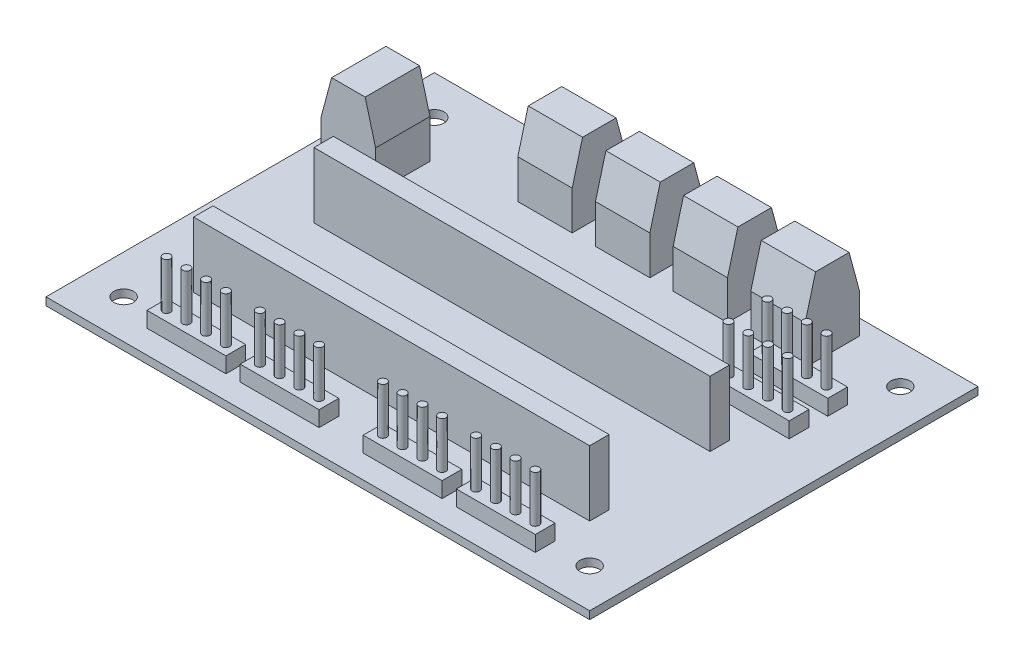
SolidWorks part; units mm, degrees
material "ABS"
ref_plane "Спереди" through (0, 0, 0) normal (0, 0, 1) x (1, 0, 0)
ref_plane "Сверху" through (0, 0, 0) normal (0, 1, 0) x (1, 0, 0)
ref_plane "Справа" through (0, 0, 0) normal (1, 0, 0) x (0, 0, -1)
sketch "Эскиз2" plane through (0, 0, 0) normal (0, 1, 0) x (1, 0, 0)
  line L0 (0, 25) -> (113.3637, 25) construction
  line L1 (0, 0) -> (70, 0)
  line L2 (0, 0) -> (0, 50)
  line L3 (0, 50) -> (70, 50)
  line L4 (70, 0) -> (70, 50)
  line L5 (35, 50) -> (35, -7.1391) construction
  circle A0 centre (5, 45) radius 1.25
  circle A1 centre (65, 45) radius 1.25
  circle A2 centre (65, 5) radius 1.25
  circle A3 centre (5, 5) radius 1.25
  dimension "D3" = 2.5
  dimension "D1" = 70
  dimension "D2" = 50
  dimension "D4" = 5
  dimension "D5" = 5
extrude "Бобышка-Вытянуть1" add sketch "Эскиз2" along normal blind 1
sketch "Эскиз3" plane through (0, 1, 0) normal (0, 1, 0) x (1, 0, 0)
  line L0 (0, 0) -> (70, 0) construction
  line L1 (9, 12.5) -> (60, 12.5)
  line L2 (9, 12.5) -> (9, 10)
  line L3 (9, 10) -> (60, 10)
  line L4 (60, 12.5) -> (60, 10)
  line L9 (70, 0) -> (70, 50) construction
  line L10 (60, 12.5) -> (60, 19) construction
  line L11 (60, 19) -> (7.0253, 19) construction
  line L12 (9, 28) -> (60, 28)
  line L13 (60, 25.5) -> (60, 28)
  line L14 (9, 25.5) -> (60, 25.5)
  line L15 (9, 25.5) -> (9, 28)
  dimension "D1" = 2.5
  dimension "D2" = 51
  dimension "D6" = 10
  dimension "D7" = 10
extrude "Бобышка-Вытянуть2" add sketch "Эскиз3" along normal blind 8.4
sketch "Эскиз4" plane through (0, 1, 0) normal (0, 1, 0) x (1, 0, 0)
  line L0 (70, 0) -> (70, 50) construction
  line L1 (60, 5.54) -> (49.84, 5.54)
  line L2 (60, 5.54) -> (60, 3)
  line L3 (60, 3) -> (49.84, 3)
  line L4 (49.84, 5.54) -> (49.84, 3)
  line L5 (0, 0) -> (70, 0) construction
  line L6 (48, 5.54) -> (48, 3)
  line L7 (35, 0) -> (35, 38.4524) construction
  line L8 (48, 5.54) -> (37.84, 5.54)
  line L9 (37.84, 5.54) -> (37.84, 3)
  line L10 (48, 3) -> (37.84, 3)
  line L11 (10, 3) -> (20.16, 3)
  line L12 (20.16, 5.54) -> (20.16, 3)
  line L13 (10, 5.54) -> (20.16, 5.54)
  line L14 (10, 5.54) -> (10, 3)
  line L15 (22, 5.54) -> (32.16, 5.54)
  line L16 (32.16, 5.54) -> (32.16, 3)
  line L17 (22, 3) -> (32.16, 3)
  line L18 (22, 5.54) -> (22, 3)
  line L19 (53.4823, 37.0132) -> (63.6423, 37.0132)
  line L20 (53.4823, 37.0132) -> (53.4823, 39.5532)
  line L21 (53.4823, 39.5532) -> (63.6423, 39.5532)
  line L22 (63.6423, 37.0132) -> (63.6423, 39.5532)
  line L23 (53.5146, 32.0132) -> (63.6746, 32.0132)
  line L24 (53.5146, 32.0132) -> (53.5146, 34.5532)
  line L25 (53.5146, 34.5532) -> (63.6746, 34.5532)
  line L26 (63.6746, 32.0132) -> (63.6746, 34.5532)
  dimension "D1" = 2.54
  dimension "D2" = 10.16
  dimension "D3" = 10
  dimension "D4" = 3
  dimension "D6" = 5
  dimension "D5" = 2
extrude "Бобышка-Вытянуть3" add sketch "Эскиз4" along normal blind 2
sketch "Эскиз5" plane through (0, 3, 0) normal (0, 1, 0) x (1, 0, 0)
  line L0 (60, 3) -> (60, 5.54) construction
  line L1 (49.84, 3) -> (60, 3) construction
  line L2 (35, 0) -> (35, 20.127) construction
  line L3 (0, 0) -> (70, 0) construction
  circle A0 centre (58.73, 4.27) radius 0.5
  circle A1 centre (56.19, 4.27) radius 0.5
  circle A2 centre (53.65, 4.27) radius 0.5
  circle A3 centre (51.11, 4.27) radius 0.5
  circle A4 centre (46.73, 4.27) radius 0.5
  circle A5 centre (44.19, 4.27) radius 0.5
  circle A6 centre (41.65, 4.27) radius 0.5
  circle A7 centre (39.11, 4.27) radius 0.5
  circle A8 centre (25.81, 4.27) radius 0.5
  circle A9 centre (11.27, 4.27) radius 0.5
  circle A10 centre (13.81, 4.27) radius 0.5
  circle A11 centre (16.35, 4.27) radius 0.5
  circle A12 centre (18.89, 4.27) radius 0.5
  circle A13 centre (23.27, 4.27) radius 0.5
  circle A14 centre (28.35, 4.27) radius 0.5
  circle A15 centre (30.89, 4.27) radius 0.5
  circle A16 centre (54.671, 33.2084) radius 0.5
  circle A17 centre (54.671, 38.2084) radius 0.5
  circle A20 centre (57.211, 33.2084) radius 0.5
  circle A21 centre (59.751, 33.2084) radius 0.5
  circle A22 centre (62.291, 33.2084) radius 0.5
  circle A23 centre (57.211, 38.2084) radius 0.5
  circle A24 centre (59.751, 38.2084) radius 0.5
  circle A25 centre (62.291, 38.2084) radius 0.5
  dimension "D1" = 1
  dimension "D2" = 1.27
  dimension "D3" = 1.27
  dimension "D4" = 4
  dimension "D5" = 2
  dimension "D6" = 4
  dimension "D7" = 2
extrude "Бобышка-Вытянуть4" add sketch "Эскиз5" along normal blind 6
sketch "Эскиз6" plane through (0, 1, 0) normal (0, 1, 0) x (1, 0, 0)
  line L0 (19.7472, 48.0002) -> (26.7472, 48.0002)
  line L5 (2.608, 39.8256) -> (9.608, 39.8256)
  line L6 (2.608, 39.8256) -> (2.608, 32.8256)
  line L7 (2.608, 32.8256) -> (9.608, 32.8256)
  line L8 (9.608, 39.8256) -> (9.608, 32.8256)
  line L9 (19.7472, 48.0002) -> (19.7472, 41.0002)
  line L10 (19.7472, 41.0002) -> (26.7472, 41.0002)
  line L11 (26.7472, 48.0002) -> (26.7472, 41.0002)
  line L12 (29.7472, 48.0002) -> (36.7472, 48.0002)
  line L13 (36.7472, 48.0002) -> (36.7472, 41.0002)
  line L14 (29.7472, 41.0002) -> (36.7472, 41.0002)
  line L15 (29.7472, 48.0002) -> (29.7472, 41.0002)
  line L16 (39.7472, 48.0002) -> (46.7472, 48.0002)
  line L17 (46.7472, 48.0002) -> (46.7472, 41.0002)
  line L18 (39.7472, 41.0002) -> (46.7472, 41.0002)
  line L19 (39.7472, 48.0002) -> (39.7472, 41.0002)
  line L20 (49.7472, 48.0002) -> (56.7472, 48.0002)
  line L21 (56.7472, 48.0002) -> (56.7472, 41.0002)
  line L22 (49.7472, 41.0002) -> (56.7472, 41.0002)
  line L23 (49.7472, 48.0002) -> (49.7472, 41.0002)
  dimension "D1" = 7
  dimension "D2" = 7
  dimension "D3" = 4
extrude "Бобышка-Вытянуть5" add sketch "Эскиз6" along normal blind 10
chamfer "Фаска1" distance 5 angle 15 10 edges at (53.2472, 11, -48.0002) (53.2472, 11, -41.0002) (43.2472, 11, -48.0002) (43.2472, 11, -41.0002) (33.2472, 11, -41.0002) (33.2472, 11, -48.0002) (23.2472, 11, -48.0002) (23.2472, 11, -41.0002) (9.608, 11, -36.3256) (2.608, 11, -36.3256) first distance on face at (53.2472, 6, -48.0002) first distance on face at (53.2472, 6, -41.0002) first distance on face at (43.2472, 6, -48.0002) first distance on face at (43.2472, 6, -41.0002) first distance on face at (33.2472, 6, -41.0002) first distance on face at (33.2472, 6, -48.0002) first distance on face at (23.2472, 6, -48.0002) first distance on face at (23.2472, 6, -41.0002) first distance on face at (9.608, 6, -36.3256) first distance on face at (2.608, 6, -36.3256)
